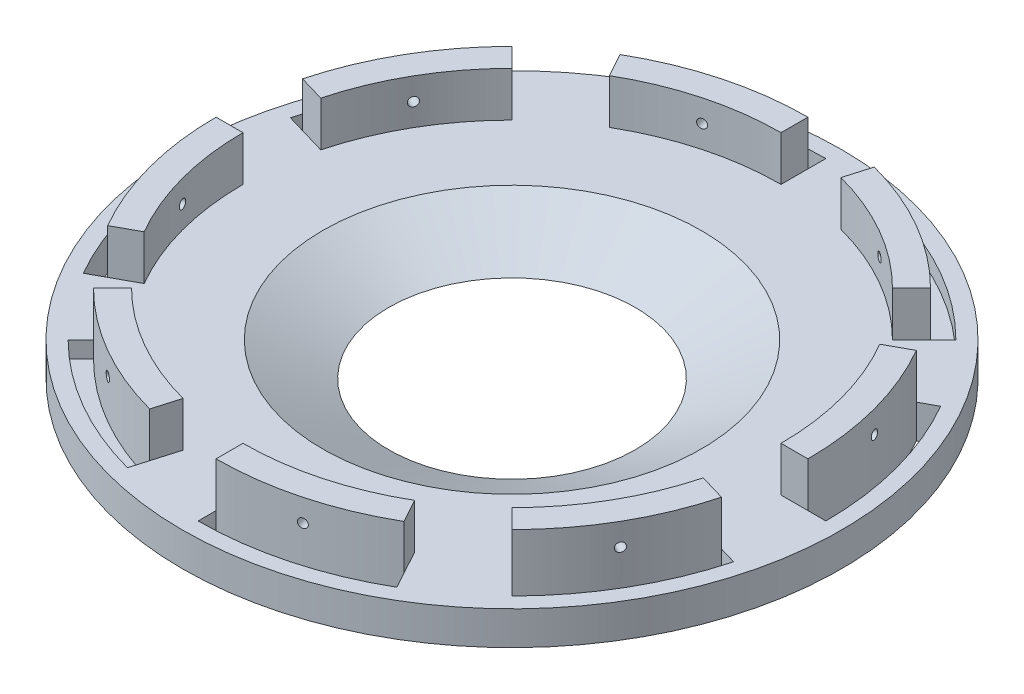
SolidWorks part; units mm, degrees
material "6061-T6 (SS)"
ref_plane "Front Plane" through (0, 0, 0) normal (0, 0, 1) x (1, 0, 0)
ref_plane "Top Plane" through (0, 0, 0) normal (0, 1, 0) x (1, 0, 0)
ref_plane "Right Plane" through (0, 0, 0) normal (1, 0, 0) x (0, 0, -1)
sketch "Sketch1" plane through (0, 0, 0) normal (0, 1, 0) x (1, 0, 0)
  circle A0 centre (0, 0) radius 93.345
  dimension "D1" = 186.69
extrude "Base" add sketch "Sketch1" along normal blind 4.7625 and the other way blind 4.7625
sketch "Sketch2" plane through (0, 4.7625, 0) normal (0, 1, 0) x (1, 0, 0)
  line L0 (0, 0) -> (0, 93.345) construction
  line L1 (-55, 0) -> (55, 0) construction
  line L2 (0, 88.9) -> (0, 83.82)
  line L3 (-41.9567, 72.5633) -> (-44.3929, 77.0226)
  line L4 (0, 0) -> (0, 93.345) construction
  arc A0 (-41.9567, 72.5633) -> (0, 83.82) centre (0, 0) cw
  arc A1 (-44.3929, 77.0226) -> (0, 88.9) centre (0, 0) cw
  circle A8 centre (0, 0) radius 93.345 construction
  dimension "D1" = 83.82
  dimension "D3" = 43.942
  dimension "D4" = 46.482
  dimension "D2" = 88.9
extrude "Bottom support holes" cut sketch "Sketch2" against normal through all
sketch "Sketch3" plane through (0, 4.7625, 0) normal (0, 1, 0) x (1, 0, 0)
  line L0 (0, 0) -> (0, 93.345) construction
  line L2 (0, 83.82) -> (0, 76.2)
  line L3 (-38.3023, 65.8739) -> (-41.9567, 72.5633)
  line L4 (-55, 0) -> (55, 0) construction
  line L7 (-44.3929, 77.0226) -> (-41.9567, 72.5633) construction
  arc A0 (-38.3023, 65.8739) -> (0, 76.2) centre (0, 0) cw
  arc A1 (-41.9567, 72.5633) -> (0, 83.82) centre (0, 0) cw
  circle A2 centre (0, 0) radius 93.345 construction
  dimension "D1" = 76.2
  dimension "D4" = 43.942
  dimension "D2" = 83.82
extrude "Bottom support guide" add sketch "Sketch3" along normal blind 12.7
ref_plane "Bottom bolt hole plane" through (-20.9784, 0, -78.1916) normal (-0.2591, 0, -0.9658) x (-0.9658, 0, 0.2591)
sketch "Sketch6" plane through (-20.9784, 0, -78.1916) normal (-0.2591, 0, -0.9658) x (-0.9658, 0, 0.2591)
  line L0 (22.9177, 4.7625) -> (-23.0366, 4.7625) construction
  line L1 (-21.7203, 4.7625) -> (-21.7203, 17.4625) construction
  circle A0 centre (-0.0033, 11.1125) radius 1.27
  dimension "D1" = 2.54
  dimension "D2" = 6.35
  dimension "D3" = 21.717
extrude "Bottom bolt hole" cut sketch "Sketch6" against normal blind 12.7 and the other way blind 12.7
sketch "Sketch8" plane through (-31.123, 4.7625, 77.2967) normal (0, 1, 0) x (1, 0, 0)
  line L0 (31.123, 77.2967) -> (-34.8819, 143.3016) construction
  line L2 (-31.7388, 140.1585) -> (-28.1467, 136.5664)
  line L3 (-49.8549, 98.9388) -> (-54.7307, 100.3694)
  line L4 (31.123, 77.2967) -> (-34.8819, 143.3016) construction
  line L5 (31.123, 77.2967) -> (31.123, 170.6417) construction
  arc A0 (-49.8549, 98.9388) -> (-28.1467, 136.5664) centre (31.123, 77.2967) cw
  arc A1 (-54.7307, 100.3694) -> (-31.7388, 140.1585) centre (31.123, 77.2967) cw
  circle A3 centre (31.123, 77.2967) radius 93.345 construction
  dimension "D1" = 83.82
  dimension "D3" = 43.942
  dimension "D4" = 46.482
  dimension "D2" = 88.9
  dimension "D5" = 45
extrude "Top support holes" cut sketch "Sketch8" against normal blind 4.7625
sketch "Sketch10" plane through (-31.123, 4.7625, 77.2967) normal (0, 1, 0) x (1, 0, 0)
  line L0 (31.123, 77.2967) -> (-34.8819, 143.3016) construction
  line L2 (-28.1467, 136.5664) -> (-22.7586, 131.1782)
  line L3 (-42.5407, 96.7928) -> (-49.8549, 98.9388)
  line L7 (-54.7307, 100.3694) -> (-49.8549, 98.9388) construction
  arc A0 (-42.5407, 96.7928) -> (-22.7586, 131.1782) centre (31.123, 77.2967) cw
  arc A1 (-49.8549, 98.9388) -> (-28.1467, 136.5664) centre (31.123, 77.2967) cw
  dimension "D1" = 76.2
  dimension "D4" = 43.942
  dimension "D2" = 83.82
extrude "Top support guide" add sketch "Sketch10" along normal blind 12.7
ref_plane "Top bolt hole plane" through (-70.1238, 0, -40.4559) normal (-0.8662, 0, -0.4997) x (-0.4997, 0, 0.8662)
sketch "Sketch12" plane through (-70.1238, 0, -40.4559) normal (-0.8662, 0, -0.4997) x (-0.4997, 0, 0.8662)
  line L0 (22.9177, 4.7625) -> (-23.0366, 4.7625) construction
  line L1 (-21.7203, 4.7625) -> (-21.7203, 17.4625) construction
  circle A0 centre (-0.0033, 11.1125) radius 1.27
  dimension "D1" = 2.54
  dimension "D2" = 6.35
  dimension "D3" = 21.717
extrude "Top bolt hole" cut sketch "Sketch12" against normal blind 12.7 and the other way blind 12.7
pattern_circular "Bottom pattern" count 4 over 360 about axis through (0, 4.7625, 0) along (0, 1, 0) of "Bottom support holes", "Bottom support guide", "Bottom bolt hole"
pattern_circular "CirPattern3" count 4 over 360 about axis through (0, 4.7625, 0) along (0, 1, 0) of "Top support holes", "Top bolt hole", "Top support guide"
sketch "Sketch13" plane through (0, 4.7625, 0) normal (0, 1, 0) x (1, 0, 0)
  circle A0 centre (0, 0) radius 34.925
  dimension "D1" = 69.85
extrude "Cut-Extrude5" cut sketch "Sketch13" against normal blind 12.7
sketch "Sketch14" plane through (0, 0, 0) normal (0, 0, 1) x (1, 0, 0)
  line L0 (34.925, 4.7625) -> (34.925, -4.7625)
  line L1 (34.925, 4.7625) -> (53.6189, 4.7625)
  line L2 (0, 25.4) -> (0, 0) construction
  line L3 (53.6189, 4.7625) -> (34.925, -4.7625)
  line L4 (34.925, 4.7625) -> (-34.925, 4.7625) construction
  line L5 (-34.925, -4.7625) -> (34.925, -4.7625) construction
  dimension "D1" = 25.4
  dimension "D2" = 27
  dimension "D3" = 34.925
revolve "Cut-Revolve1" cut sketch "Sketch14" angle 360 about L2
